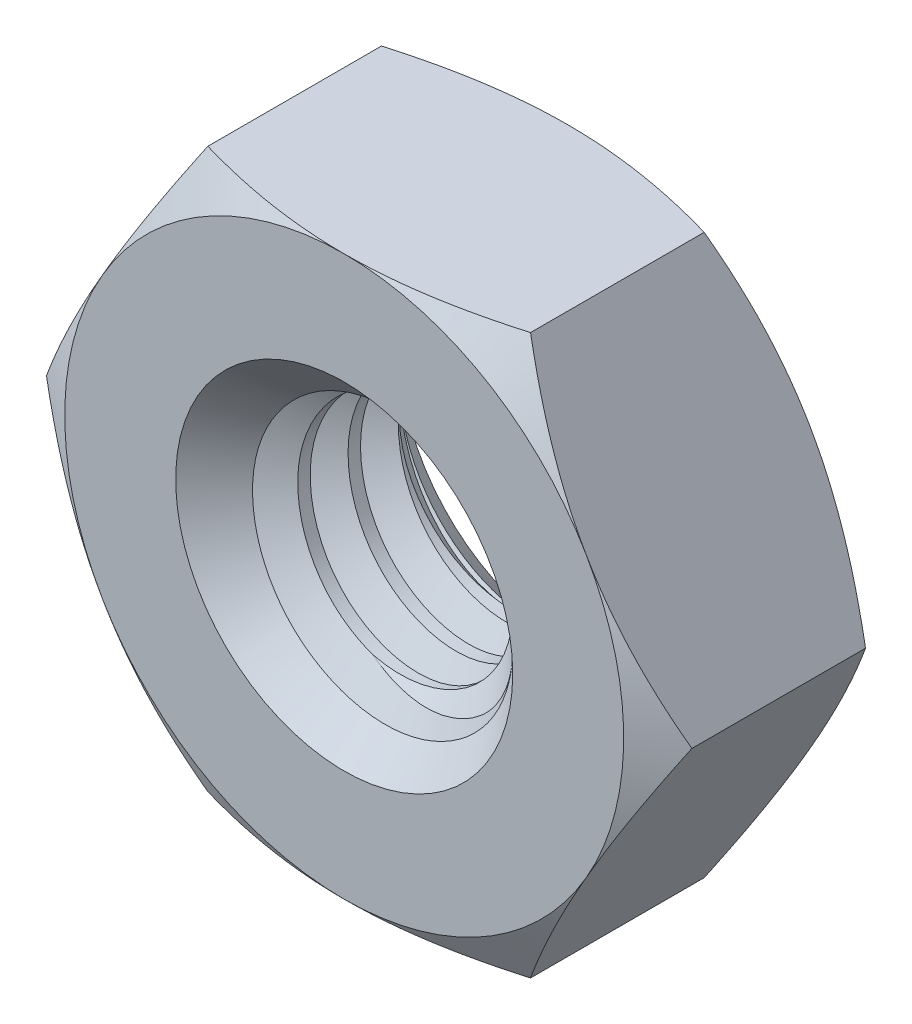
SolidWorks part; units mm, degrees
ref_plane "Front" through (0, 0, 0) normal (0, 0, 1) x (1, 0, 0)
ref_plane "Top" through (0, 0, 0) normal (0, 1, 0) x (1, 0, 0)
ref_plane "Right" through (0, 0, 0) normal (1, 0, 0) x (0, 0, -1)
sketch "Çizim1" plane through (0, 0, 0) normal (0, 0, 1) x (1, 0, 0)
  line L1 (2.8868, 0) -> (1.4434, 2.5)
  line L2 (1.4434, 2.5) -> (-1.4434, 2.5)
  line L3 (-1.4434, 2.5) -> (-2.8868, 0)
  line L4 (-2.8868, 0) -> (-1.4434, -2.5)
  line L5 (-1.4434, -2.5) -> (1.4434, -2.5)
  line L6 (1.4434, -2.5) -> (2.8868, 0)
  circle A0 centre (0, 0) radius 2.5 construction
  point P1 (0, 0)
  dimension "D1" = 5
extrude "Yükseklik-Ekstrüzyon1" add sketch "Çizim1" along normal blind 2
sketch "Çizim2" plane through (0, 0, 2) normal (0, 0, 1) x (1, 0, 0)
  circle A0 centre (0, 0) radius 2.5
extrude "Kes-Ekstrüzyon1" cut sketch "Çizim2" against normal blind 2 draft 60 flip side to cut
sketch "Çizim3" plane through (0, 0, 0) normal (0, 0, -1) x (-1, 0, 0)
  circle A0 centre (0, 0) radius 2.5
extrude "Kes-Ekstrüzyon2" cut sketch "Çizim3" against normal blind 2 draft 60 flip side to cut
sketch "Çizim4" plane through (0, 0, 0) normal (0, 0, -1) x (-1, 0, 0)
  circle A0 centre (0, 0) radius 1.0075
  dimension "D1" = 2.015
extrude "Kes-Ekstrüzyon3" cut sketch "Çizim4" against normal blind 2
chamfer "Pah1" distance 0.5 angle 45 2 edges at (-1.0075, 0, 2) (-1.0075, 0, 0)
sketch "Çizim6" plane through (0, 0, 0) normal (0, 0, -1) x (-1, 0, 0)
  circle A0 centre (0, 0) radius 1.0075
curve "Helis/Spiral1" pitch 0.45 height 3 radius 1.0075 centre (0, 0, 0) axis (0, 0, 1) start towards (1, 0, 0)
ref_plane "Düzlem1" through (-0.5037, -0.8725, 3) normal (0.8638, -0.4987, 0.0709) x (0.0614, -0.0355, -0.9975)
sketch "Çizim7" plane through (-0.5037, -0.8725, 3) normal (0.8638, -0.4987, 0.0709) x (0.0614, -0.0355, -0.9975)
  line L0 (0.2096, 0.0706) -> (-0.2096, 0.0706)
  line L1 (0, -0.2925) -> (0.2096, 0.0706)
  line L3 (-0.2096, 0.0706) -> (0, -0.2925)
  line L5 (0, 0.1463) -> (-0.2533, 0.1462) [skipped]
  circle A0 centre (0, 0) radius 0.1463 construction
  dimension "D1" = 0.2925
sweep "Kes-Süpür1" cut profiles "Çizim7" path "Helis/Spiral1" align with end faces yes
